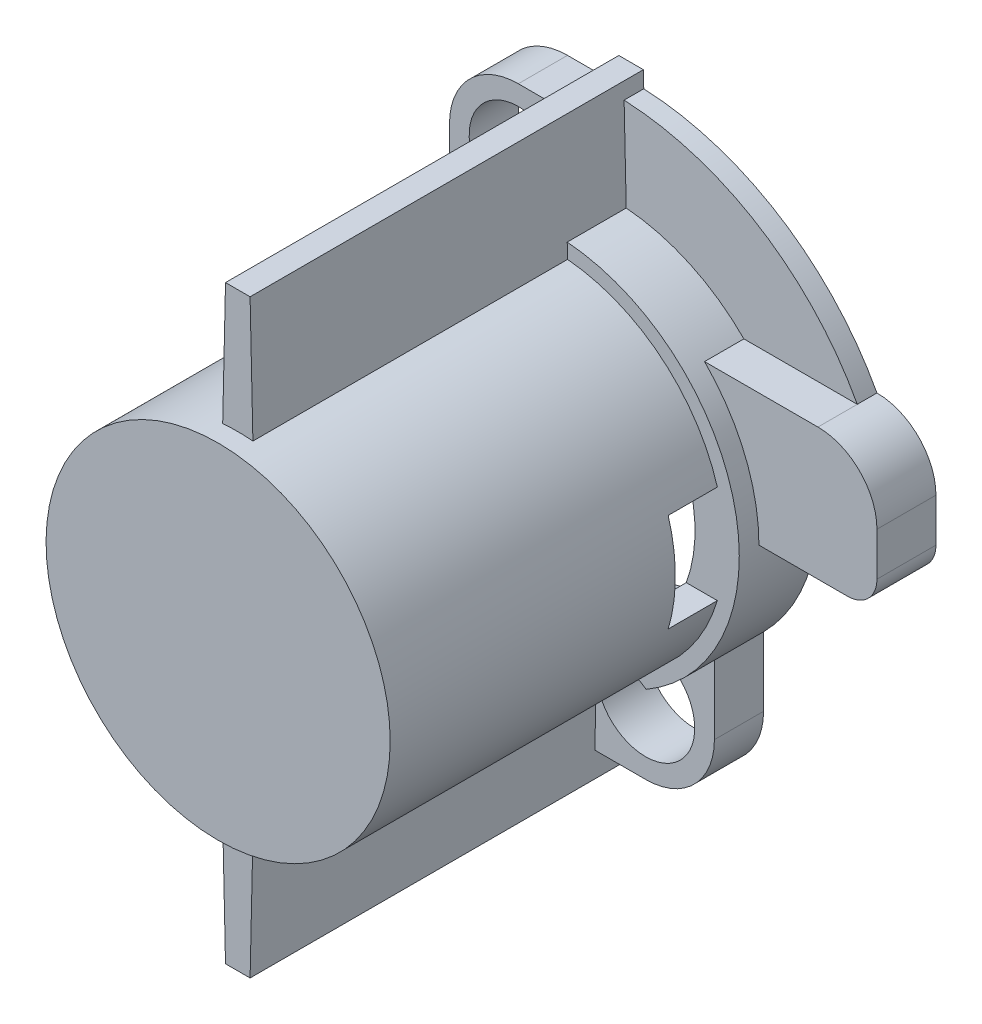
SolidWorks part; units mm, degrees
ref_plane "Front Plane" through (0, 0, 0) normal (0, 0, 1) x (1, 0, 0)
ref_plane "Top Plane" through (0, 0, 0) normal (0, 1, 0) x (1, 0, 0)
ref_plane "Right Plane" through (0, 0, 0) normal (1, 0, 0) x (0, 0, -1)
sketch "Sketch1" plane through (0, 0, 0) normal (0, 0, 1) x (1, 0, 0)
  line L0 (-19, 0) -> (19, 0) construction
  line L2 (-13.47, 13.4) -> (-13.47, 27.4)
  line L3 (-13.47, 27.4) -> (0.53, 27.4)
  line L4 (0.53, 13.4) -> (0.53, 27.4)
  line L5 (-6.47, 27.4) -> (-6.47, 13.4) construction
  line L6 (-13.47, 20.4) -> (0.53, 20.4) construction
  line L7 (0, 0) -> (0, 19) construction
  line L8 (-1.25, 30) -> (1.25, 30)
  line L9 (-1.25, 30) -> (-1.5363, 17.4324)
  line L10 (1.25, 30) -> (1.5363, 17.4324)
  line L12 (1.25, -30) -> (1.5363, -17.4324)
  line L13 (-1.25, -30) -> (-1.5363, -17.4324)
  line L14 (-1.25, -30) -> (1.25, -30)
  line L21 (6.47, -27.4) -> (6.47, -13.4) construction
  line L23 (13.47, -13.4) -> (13.47, -27.4)
  line L24 (13.47, -27.4) -> (-0.53, -27.4)
  line L25 (-0.53, -13.4) -> (-0.53, -27.4)
  line L26 (13.47, -20.4) -> (-0.53, -20.4) construction
  line L27 (-13.47, 13.4) -> (0.53, 13.4)
  line L28 (13.47, -13.4) -> (-0.53, -13.4)
  line L29 (-19, 0) -> (-28, 0)
  line L30 (-31, -3) -> (-31, -7.4)
  line L31 (-25, -13.4) -> (-13.47, -13.4)
  line L32 (19, 0) -> (28, 0)
  line L33 (31, 3) -> (31, 7.4)
  line L34 (25, 13.4) -> (13.47, 13.4)
  circle A0 centre (0, 0) radius 19
  circle A1 centre (0, 0) radius 20 construction
  circle A2 centre (-6.47, 20.4) radius 5
  circle A3 centre (0, 0) radius 17.5
  circle A6 centre (6.47, -20.4) radius 5
  arc A7 (31, 7.4) -> (25, 13.4) centre (25, 7.4) ccw
  arc A8 (-31, -7.4) -> (-25, -13.4) centre (-25, -7.4) ccw
  arc A9 (28, 0) -> (31, 3) centre (28, 3) ccw
  arc A10 (-28, 0) -> (-31, -3) centre (-28, -3) ccw
  arc A11 (-25, -13.4) -> (-1.2879, -28.3355) centre (0, 0) ccw
  arc A12 (25, 13.4) -> (1.2879, 28.3355) centre (0, 0) ccw
  point P20 (0, 30)
  point P51 (-31, 0)
  dimension "D1" = 38
  dimension "D2" = 40
  dimension "D5" = 10
  dimension "D7" = 35
  dimension "D11" = 30
  dimension "D8" = 10
  dimension "D13" = 6
  dimension "D14" = 3
  dimension "D3" = 5.53
  dimension "D4" = 14
  dimension "D6" = 2.5
  dimension "D9" = 14
  dimension "D10" = 5.53
  dimension "D12" = 12
extrude "Boss-Extrude1" add sketch "Sketch1" along normal blind 5 contours A2 L9 L3 L2 A0 | A6 L12 L24 L23 A0 region at (-13.2846, 20.4, 0) region at (1.5757, -23.8473, 0)
extrude "Boss-Extrude2" add sketch "Sketch1<3>" along normal blind 40 contours A0 L10 L8 L9 L3 L4 | A0 L4 L3 L9 | A3 L4 A0 L9 | A3 L10 A0 L4 | A3 L25 A0 L12 | A3 L13 A0 L25 | A0 L13 L14 L12 L24 L25 | A0 L25 L24 L12 region at (-1.1655, 28.6974, 0) region at (-0.4394, 23.1229, 0) region at (-1.0249, -18.2145, 0) region at (-0.4951, 18.2315, 0) region at (1.0249, 18.2145, 0) region at (-1.0224, -19.0867, 0) region at (0.4951, -18.2315, 0) region at (0.4394, -23.1229, 0)
sketch "Sketch1<3>" plane through (0, 0, 0) normal (0, 0, 1) x (1, 0, 0) same geometry as "Sketch1"
extrude "Boss-Extrude3" add sketch "Sketch1<4>" along normal blind 42 contours L27 A3 L25 L28 L4 | L4 A3 A2 L27 | A6 A3 L28 L25 region at (-3.8403, 14.9222, 0) region at (0, 0, 0) region at (3.8403, -14.9222, 0)
sketch "Sketch1<4>" plane through (0, 0, 0) normal (0, 0, 1) x (1, 0, 0) same geometry as "Sketch1"
extrude "Boss-Extrude4" add sketch "Sketch1<5>" along normal blind 8 contours A3 L27 A0 L13 | A3 L28 A0 L10 | A3 A2 A0 L27 | A2 A0 L9 | A3 L9 A0 A2 | A6 A0 L12 | A6 A3 L12 A0 | A6 A0 L28 A3 region at (-10.669, 14.7797, 0) region at (-12.3629, 13.0323, 0) region at (-1.5512, 19.2694, 0) region at (-1.8374, 17.9649, 0) region at (1.8867, 18.1949, 0) region at (1.8374, -17.9649, 0) region at (1.5512, -19.2694, 0) region at (10.669, -14.7797, 0)
sketch "Sketch1<5>" plane through (0, 0, 0) normal (0, 0, 1) x (1, 0, 0) same geometry as "Sketch1"
extrude "Boss-Extrude5" add sketch "Sketch1<6>" along normal blind 6 contours L29 A10 L30 A8 L31 A0 | L32 A9 L33 A7 L34 A0 region at (-23.7273, -6.9865, 0) region at (23.7273, 6.9865, 0)
sketch "Sketch1<6>" plane through (0, 0, 0) normal (0, 0, 1) x (1, 0, 0) same geometry as "Sketch1"
extrude "Boss-Extrude6" add sketch "Sketch1<7>" along normal blind 2 contours L31 A11 L13 A0 | L34 A12 L10 A0 region at (-11.6168, -20.2864, 0) region at (11.6168, 20.2864, 0)
sketch "Sketch1<7>" plane through (0, 0, 0) normal (0, 0, 1) x (1, 0, 0) same geometry as "Sketch1"
fillet "Fillet1" radius 7 2 edges at (13.47, -27.4, 2.5) (-13.47, 27.4, 2.5)
extrude "Boss-Extrude7" add sketch "Sketch1<8>" along normal blind 42 contours A2 A3 | A3 A6 region at (-5.1428, 16.2154, 0) region at (5.1428, -16.2154, 0)
sketch "Sketch1<8>" plane through (0, 0, 0) normal (0, 0, 1) x (1, 0, 0) same geometry as "Sketch1"
sketch "Sketch2" plane through (0, 0, 0) normal (0, 0, -1) x (-1, 0, 0)
  circle A0 centre (0, 0) radius 14.5
  dimension "D1" = 29
extrude "Cut-Extrude1" cut sketch "Sketch2" against normal blind 40
ref_plane "Plane1" through (-17.5, 0, 0) normal (-1, 0, 0) x (0, 0, 1)
sketch "Sketch3" plane through (-17.5, 0, 0) normal (-1, 0, 0) x (0, 0, 1)
  line L0 (8, -18.9405) -> (8, 16.4408) construction
  line L1 (8, 5) -> (13, 5)
  line L2 (8, 5) -> (8, -5)
  line L3 (8, -5) -> (13, -5)
  line L4 (13, 5) -> (13, -5)
  point P4 (13, 0)
  dimension "D1" = 10
  dimension "D2" = 5
extrude "Cut-Extrude2" cut sketch "Sketch3" against normal blind 40
